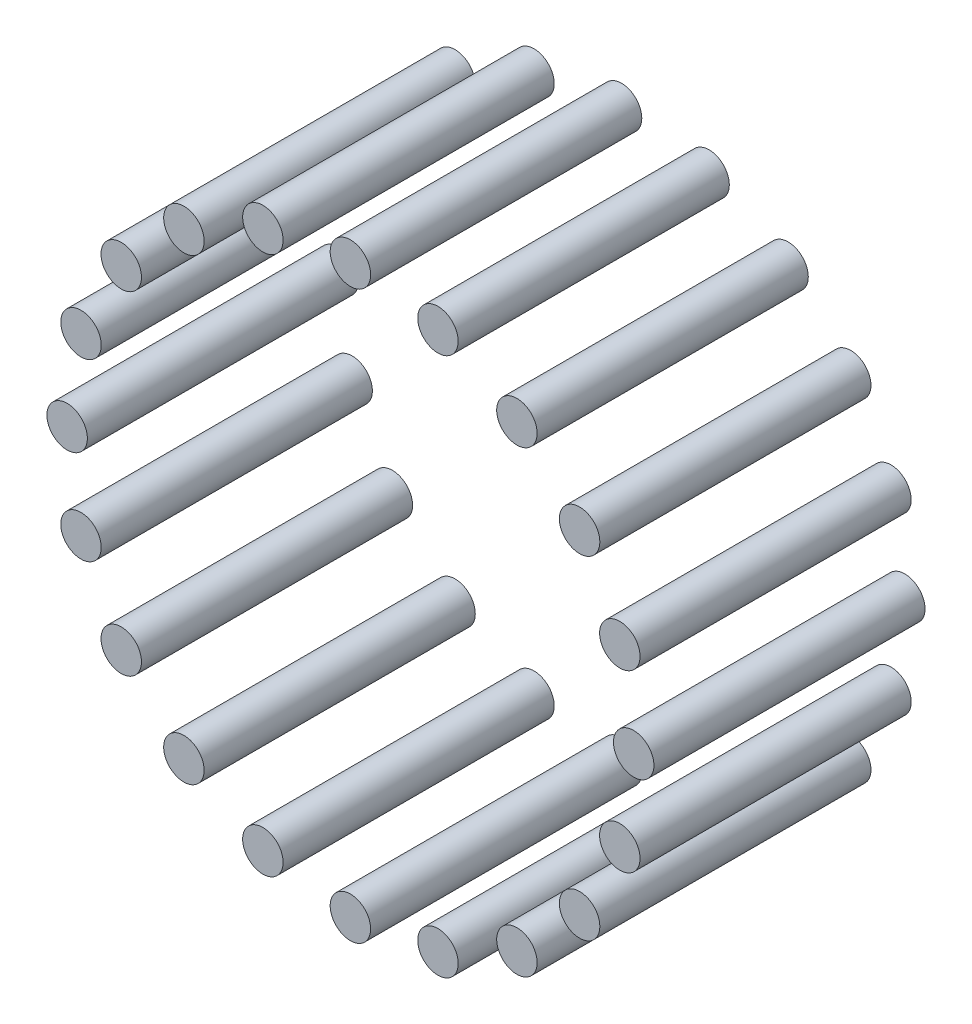
SolidWorks part; units mm, degrees
ref_plane "Front" through (0, 0, 0) normal (0, 0, 1) x (1, 0, 0)
ref_plane "Top" through (0, 0, 0) normal (0, 1, 0) x (1, 0, 0)
ref_plane "Right" through (0, 0, 0) normal (1, 0, 0) x (0, 0, -1)
sketch "Sketch1" plane through (0, 0, 0) normal (0, 0, 1) x (1, 0, 0)
  line L0 (0, 0) -> (0, 35) construction
  circle A0 centre (0, 35) radius 2.5
  circle A1 centre (10.8156, 33.287) radius 2.5
  circle A2 centre (20.5725, 28.3156) radius 2.5
  circle A3 centre (28.3156, 20.5725) radius 2.5
  circle A4 centre (33.287, 10.8156) radius 2.5
  circle A5 centre (35, 0) radius 2.5
  circle A6 centre (33.287, -10.8156) radius 2.5
  circle A7 centre (28.3156, -20.5725) radius 2.5
  circle A8 centre (20.5725, -28.3156) radius 2.5
  circle A9 centre (10.8156, -33.287) radius 2.5
  circle A10 centre (0, -35) radius 2.5
  circle A11 centre (-10.8156, -33.287) radius 2.5
  circle A12 centre (-20.5725, -28.3156) radius 2.5
  circle A13 centre (-28.3156, -20.5725) radius 2.5
  circle A14 centre (-33.287, -10.8156) radius 2.5
  circle A15 centre (-35, 0) radius 2.5
  circle A16 centre (-33.287, 10.8156) radius 2.5
  circle A17 centre (-28.3156, 20.5725) radius 2.5
  circle A18 centre (-20.5725, 28.3156) radius 2.5
  circle A19 centre (-10.8156, 33.287) radius 2.5
  dimension "D1" = 5
  dimension "D2" = 35
  dimension "D3" = 20
extrude "Boss-Extrude1" add sketch "Sketch1" along normal blind 33.5
ref_axis "Axis1" through (0, 0, 50) along (0, 0, -1)
